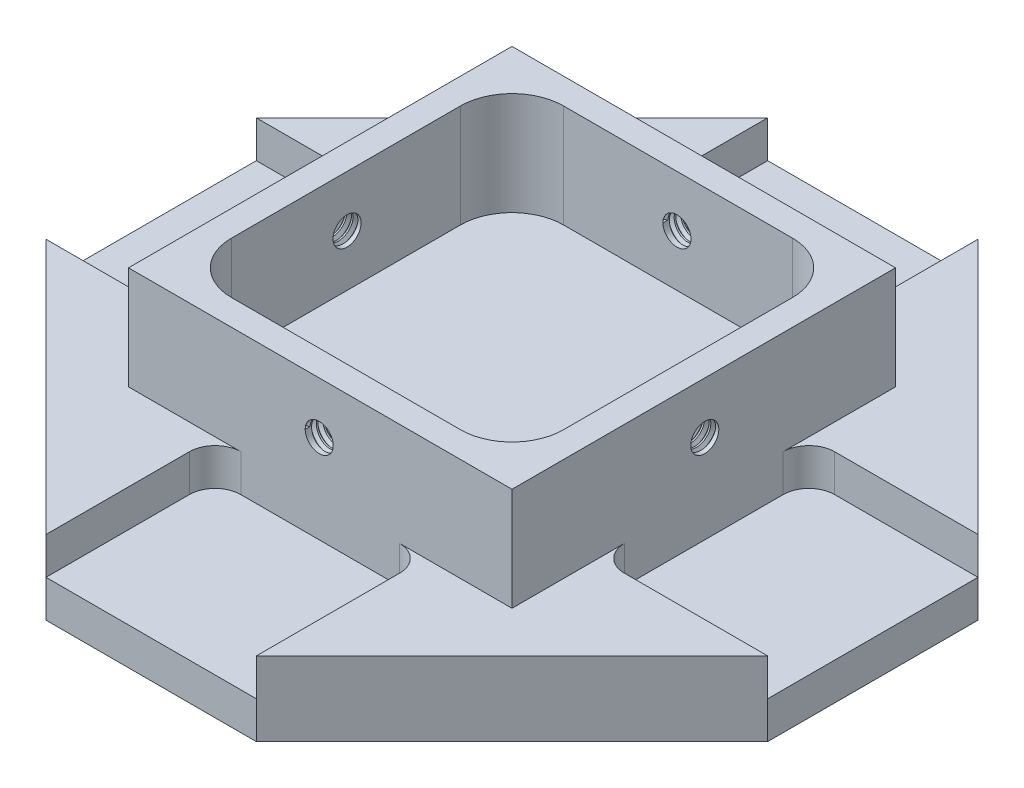
SolidWorks part; units mm, degrees
material "6061 Alloy"
ref_plane "Front Plane" through (0, 0, 0) normal (0, 0, 1) x (1, 0, 0)
ref_plane "Top Plane" through (0, 0, 0) normal (0, 1, 0) x (1, 0, 0)
ref_plane "Right Plane" through (0, 0, 0) normal (1, 0, 0) x (0, 0, -1)
sketch "Sketch1" plane through (0, 0, 0) normal (0, 1, 0) x (1, 0, 0)
  line L1 (0, 0) -> (88.9, 0)
  line L2 (0, 0) -> (0, 88.9)
  line L3 (0, 88.9) -> (88.9, 88.9)
  line L4 (88.9, 0) -> (88.9, 88.9)
  dimension "D1" = 88.9
  dimension "D2" = 88.9
extrude "Boss-Extrude1" add sketch "Sketch1" along normal blind 9.144
sketch "Sketch2" plane through (0, 9.144, 0) normal (0, 1, 0) x (1, 0, 0)
  line L0 (88.9, 88.9) -> (0, 88.9) construction
  line L1 (31.496, 88.9) -> (57.404, 88.9)
  line L2 (31.496, 88.9) -> (31.496, 67.31)
  line L3 (31.496, 67.31) -> (57.404, 67.31)
  line L4 (57.404, 88.9) -> (57.404, 67.31)
  line L5 (0, 88.9) -> (0, 0) construction
  line L6 (0, 57.404) -> (21.59, 57.404)
  line L7 (0, 57.404) -> (0, 31.496)
  line L8 (0, 31.496) -> (21.59, 31.496)
  line L9 (21.59, 57.404) -> (21.59, 31.496)
  line L10 (0, 0) -> (88.9, 0) construction
  line L11 (31.496, 0) -> (57.404, 0)
  line L12 (31.496, 0) -> (31.496, 21.59)
  line L13 (31.496, 21.59) -> (57.404, 21.59)
  line L14 (57.404, 0) -> (57.404, 21.59)
  line L15 (88.9, 0) -> (88.9, 88.9) construction
  line L16 (88.9, 57.404) -> (67.31, 57.404)
  line L17 (88.9, 57.404) -> (88.9, 31.496)
  line L18 (88.9, 31.496) -> (67.31, 31.496)
  line L19 (67.31, 57.404) -> (67.31, 31.496)
  dimension "D1" = 31.496
  dimension "D2" = 25.908
  dimension "D3" = 25.908
  dimension "D4" = 31.496
  dimension "D5" = 25.908
  dimension "D6" = 31.496
  dimension "D7" = 25.908
  dimension "D8" = 31.496
  dimension "D9" = 21.59
  dimension "D10" = 21.59
  dimension "D11" = 21.59
  dimension "D12" = 21.59
extrude "Cut-Extrude1" cut sketch "Sketch2" against normal blind 4.572
sketch "Sketch3" plane through (0, 9.144, 0) normal (0, 1, 0) x (1, 0, 0)
  line L0 (31.496, 88.9) -> (0, 88.9) construction
  line L1 (20.6375, 68.2625) -> (68.2625, 68.2625)
  line L2 (20.6375, 68.2625) -> (20.6375, 20.6375)
  line L3 (20.6375, 20.6375) -> (68.2625, 20.6375)
  line L4 (68.2625, 68.2625) -> (68.2625, 20.6375)
  line L5 (0, 31.496) -> (0, 0) construction
  line L6 (88.9, 31.496) -> (88.9, 57.404) construction
  line L7 (57.404, 88.9) -> (31.496, 88.9) construction
  line L8 (0, 57.404) -> (0, 31.496) construction
  line L9 (31.496, 0) -> (57.404, 0) construction
  circle A0 centre (28.194, 44.45) radius 2.4
  circle A1 centre (44.45, 60.706) radius 2.4
  circle A2 centre (60.706, 44.45) radius 2.4
  circle A3 centre (44.45, 28.194) radius 2.4
  dimension "D5" = 4.8
  dimension "D6" = 4.8
  dimension "D7" = 4.8
  dimension "D8" = 4.8
  dimension "D1" = 47.625
  dimension "D2" = 47.625
  dimension "D3" = 20.6375
  dimension "D4" = 20.6375
  dimension "D9" = 28.194
  dimension "D10" = 28.194
  dimension "D11" = 28.194
  dimension "D12" = 28.194
  dimension "D13" = 23.8125
  dimension "D14" = 23.8125
  dimension "D15" = 23.8125
  dimension "D16" = 23.8125
extrude "Cut-Extrude2" [suppressed] cut sketch "Sketch3" against normal through all contours A2 | A1 | A0 | A3
sketch "Sketch4" plane through (0, 4.572, 0) normal (0, 1, 0) x (1, 0, 0)
  line L0 (0, 57.404) -> (0, 31.496) construction
  line L1 (57.404, 88.9) -> (31.496, 88.9) construction
  line L2 (88.9, 31.496) -> (88.9, 57.404) construction
  line L3 (31.496, 0) -> (57.404, 0) construction
  line L4 (0, 31.496) -> (21.59, 31.496) construction
  line L5 (31.496, 21.59) -> (31.496, 0) construction
  line L6 (67.31, 31.496) -> (88.9, 31.496) construction
  line L7 (57.404, 67.31) -> (57.404, 88.9) construction
  circle A0 centre (79.629, 50.3936) radius 1.8034
  circle A1 centre (79.629, 39.2684) radius 1.8034
  circle A2 centre (49.6316, 79.629) radius 1.8034
  circle A3 centre (38.5064, 79.629) radius 1.8034
  circle A4 centre (9.271, 50.3936) radius 1.8034
  circle A5 centre (9.271, 39.2684) radius 1.8034
  circle A6 centre (39.2684, 9.271) radius 1.8034
  circle A7 centre (50.3936, 9.271) radius 1.8034
  dimension "D1" = 3.6068
  dimension "D2" = 3.6068
  dimension "D3" = 3.6068
  dimension "D4" = 3.6068
  dimension "D5" = 3.6068
  dimension "D6" = 3.6068
  dimension "D7" = 3.6068
  dimension "D8" = 3.6068
  dimension "D9" = 9.271
  dimension "D10" = 9.271
  dimension "D11" = 9.271
  dimension "D12" = 9.271
  dimension "D13" = 9.271
  dimension "D14" = 9.271
  dimension ".313" = 9.271
  dimension "D16" = 9.271
  dimension "D17" = 11.1252
  dimension "D18" = 7.7724
  dimension "D19" = 7.7724
  dimension "D20" = 11.1252
  dimension "D21" = 7.7724
  dimension "D22" = 11.1252
  dimension "D23" = 7.7724
  dimension "D24" = 11.1252
extrude "Cut-Extrude3" [suppressed] cut sketch "Sketch4" against normal through all
sketch "Sketch5" plane through (0, 9.144, 0) normal (0, 1, 0) x (1, 0, 0)
  line L0 (88.9, 88.9) -> (57.404, 88.9) construction
  line L1 (88.9, 31.496) -> (88.9, 57.404) construction
  circle A0 centre (44.45, 44.45) radius 6.35
  dimension "D1" = 12.7
  dimension "D2" = 44.45
  dimension "D3" = 44.45
extrude "Cut-Extrude4" [suppressed] cut sketch "Sketch5" against normal through all
sketch "Sketch6" plane through (0, 9.144, 0) normal (0, 1, 0) x (1, 0, 0)
  line L0 (88.9, 31.496) -> (57.404, 0)
  line L1 (57.404, 0) -> (88.9, 0)
  line L2 (88.9, 0) -> (88.9, 31.496)
extrude "Cut-Extrude5" cut sketch "Sketch6" against normal through all
sketch "Sketch7" plane through (0, 9.144, 0) normal (0, 1, 0) x (1, 0, 0)
  line L0 (0, 88.9) -> (0, 57.404) construction
  line L1 (20.828, 68.072) -> (68.072, 68.072)
  line L2 (20.828, 68.072) -> (20.828, 20.828)
  line L3 (20.828, 20.828) -> (68.072, 20.828)
  line L4 (68.072, 68.072) -> (68.072, 20.828)
  line L5 (0, 0) -> (31.496, 0) construction
  line L7 (24.003, 24.003) -> (64.897, 24.003)
  line L8 (24.003, 24.003) -> (24.003, 64.897)
  line L9 (24.003, 64.897) -> (64.897, 64.897)
  line L10 (64.897, 24.003) -> (64.897, 64.897)
  dimension "D1" = 47.244
  dimension "D2" = 47.244
  dimension "D3" = 20.828
  dimension "D4" = 20.828
  dimension "D5" = 3.175
  dimension "D6" = 3.175
  dimension "D7" = 3.175
  dimension "D8" = 3.175
extrude "Boss-Extrude2" add sketch "Sketch7" along normal blind 12.7 and the other way up to next (4.572 mm away)
fillet "Fillet9" radius 6.35 1 edges at (64.897, 15.494, -24.003)
fillet "Fillet10" radius 6.35 1 edges at (24.003, 15.494, -24.003)
fillet "Fillet11" radius 6.35 1 edges at (64.897, 15.494, -64.897)
fillet "Fillet12" radius 6.35 1 edges at (24.003, 15.494, -64.897)
fillet "Fillet15" radius 3.175 1 edges at (20.828, 6.858, -57.404)
fillet "Fillet16" radius 3.175 1 edges at (31.496, 6.858, -20.828)
fillet "Fillet17" radius 3.175 1 edges at (57.404, 6.858, -20.828)
fillet "Fillet18" radius 3.175 1 edges at (68.072, 6.858, -57.404)
fillet "Fillet19" radius 3.175 1 edges at (68.072, 6.858, -31.496)
fillet "Fillet20" radius 3.175 1 edges at (31.496, 6.858, -68.072)
fillet "Fillet21" radius 3.175 1 edges at (57.404, 6.858, -68.072)
fillet "Fillet22" radius 3.175 1 edges at (20.828, 6.858, -31.496)
sketch "Sketch9" plane through (0, 0, -68.072) normal (0, 0, -1) x (-1, 0, 0)
  line L0 (-68.072, 21.844) -> (-68.072, 9.144) construction
  line L1 (-68.072, 21.844) -> (-20.828, 21.844) construction
  circle A0 centre (-44.323, 15.494) radius 1.7272
  dimension "D1" = 3.4544
  dimension "D2" = 23.749
  dimension "D3" = 6.35
extrude "Cut-Extrude6" cut sketch "Sketch9" against normal through all
sketch "Sketch10" plane through (68.072, 0, 0) normal (1, 0, 0) x (0, 0, -1)
  line L0 (20.828, 21.844) -> (68.072, 21.844) construction
  line L1 (20.828, 21.844) -> (20.828, 9.144) construction
  circle A0 centre (44.577, 15.494) radius 1.7272
  dimension "D1" = 3.4544
  dimension "D2" = 6.35
  dimension "D3" = 23.749
extrude "Cut-Extrude7" cut sketch "Sketch10" against normal through all
sketch "Sketch12" plane through (0, 9.144, 0) normal (0, 1, 0) x (1, 0, 0)
  line L0 (0, 31.496) -> (31.496, 0)
  line L1 (31.496, 0) -> (0, 0)
  line L2 (0, 0) -> (0, 31.496)
  line L3 (57.404, 88.9) -> (88.9, 57.404)
  line L4 (88.9, 57.404) -> (88.9, 88.9)
  line L5 (88.9, 88.9) -> (57.404, 88.9)
  line L6 (0, 57.404) -> (31.496, 88.9)
  line L7 (31.496, 88.9) -> (0, 88.9)
  line L8 (0, 88.9) -> (0, 57.404)
sketch "Sketch14" plane through (0, 0, 0) normal (0, -1, 0) x (1, 0, 0)
  line L0 (60.2924, -60.2924) -> (28.8616, -28.8616) construction
  line L6 (24.003, -58.547) -> (24.003, -30.353) construction
  line L7 (30.353, -24.003) -> (58.547, -24.003) construction
  circle A0 centre (28.8616, -28.8616) radius 2.54
  circle A1 centre (60.2924, -60.2924) radius 2.54
  point P0 (44.577, -44.577)
  dimension "D1" = 44.45
  dimension "D2" = 5.08
  dimension "D3" = 5.08
  dimension "D4" = 20.574
  dimension "D5" = 20.574
extrude "Cut-Extrude9" cut sketch "Sketch14" against normal through all
extrude "Cut-Extrude10" cut sketch "Sketch12" against normal through all
thread "Thread1" pitch 0.7937 method cut profile "Thread Profile1" start angle 0, offset 0, length 0, pitch 0.7937, diameter 3.4544
ref_plane "Plane1" through (42.5958, 15.494, -20.828) normal (0, -1, 0) x (-1, 0, 0)
sketch "Thread Profile1" plane through (42.5958, 15.494, -20.828) normal (0, -1, 0) x (-1, 0, 0)
  line L0 (0, 0) -> (0, 0.7937) construction
  line L1 (0, 0) -> (0.4296, 0.248)
  line L2 (0.4296, 0.248) -> (0.4296, 0.3473)
  line L3 (0.4296, 0.3473) -> (0, 0.5953)
  line L4 (0.4296, 0.2977) -> (0, 0.2977) construction
  line L11 (0, 0) -> (0, 0.5953)
  point P2 (0, 0)
  dimension "Pitch" = 0.7937
  dimension "Profile_Angle" = 60
  dimension "Profile_Land" = 0.0992
  dimension "Profile_Height" = 0.4296
thread "Thread2" pitch 0.7937 method cut profile "Thread Profile2" start angle 0, offset 0, length 0, pitch 0.7937, diameter 3.4544
ref_plane "Plane2" through (68.072, 15.494, -42.8498) normal (0, -1, 0) x (0, 0, 1)
sketch "Thread Profile2" plane through (68.072, 15.494, -42.8498) normal (0, -1, 0) x (0, 0, 1)
  line L0 (0, 0) -> (0, 0.7937) construction
  line L1 (0, 0) -> (0.4296, 0.248)
  line L2 (0.4296, 0.248) -> (0.4296, 0.3473)
  line L3 (0.4296, 0.3473) -> (0, 0.5953)
  line L4 (0.4296, 0.2977) -> (0, 0.2977) construction
  line L11 (0, 0) -> (0, 0.5953)
  point P2 (0, 0)
  dimension "Pitch" = 0.7937
  dimension "Profile_Angle" = 60
  dimension "Profile_Land" = 0.0992
  dimension "Profile_Height" = 0.4296
thread "Thread3" pitch 0.7937 method cut profile "Thread Profile3" start angle 0, offset 0, length 0, pitch 0.7937, diameter 3.4544
ref_plane "Plane3" through (42.5958, 15.494, -64.897) normal (0, -1, 0) x (-1, 0, 0)
sketch "Thread Profile3" plane through (42.5958, 15.494, -64.897) normal (0, -1, 0) x (-1, 0, 0)
  line L0 (0, 0) -> (0, 0.7937) construction
  line L1 (0, 0) -> (0.4296, 0.248)
  line L2 (0.4296, 0.248) -> (0.4296, 0.3473)
  line L3 (0.4296, 0.3473) -> (0, 0.5953)
  line L4 (0.4296, 0.2977) -> (0, 0.2977) construction
  line L11 (0, 0) -> (0, 0.5953)
  point P2 (0, 0)
  dimension "Pitch" = 0.7937
  dimension "Profile_Angle" = 60
  dimension "Profile_Land" = 0.0992
  dimension "Profile_Height" = 0.4296
thread "Thread4" pitch 0.7937 method cut profile "Thread Profile4" start angle 0, offset 0, length 0, pitch 0.7937, diameter 3.4544
ref_plane "Plane4" through (24.003, 15.494, -42.8498) normal (0, -1, 0) x (0, 0, 1)
sketch "Thread Profile4" plane through (24.003, 15.494, -42.8498) normal (0, -1, 0) x (0, 0, 1)
  line L0 (0, 0) -> (0, 0.7937) construction
  line L1 (0, 0) -> (0.4296, 0.248)
  line L2 (0.4296, 0.248) -> (0.4296, 0.3473)
  line L3 (0.4296, 0.3473) -> (0, 0.5953)
  line L4 (0.4296, 0.2977) -> (0, 0.2977) construction
  line L11 (0, 0) -> (0, 0.5953)
  point P2 (0, 0)
  dimension "Pitch" = 0.7937
  dimension "Profile_Angle" = 60
  dimension "Profile_Land" = 0.0992
  dimension "Profile_Height" = 0.4296
equation "\"hinge_hole\"= 0.142in"
equation "\"D1@Sketch4\"=\"hinge_hole\""
equation "\"D2@Sketch4\"=\"hinge_hole\""
equation "\"D3@Sketch4\"=\"hinge_hole\""
equation "\"D4@Sketch4\"=\"hinge_hole\""
equation "\"D5@Sketch4\"=\"hinge_hole\""
equation "\"D6@Sketch4\"=\"hinge_hole\""
equation "\"D7@Sketch4\"=\"hinge_hole\""
equation "\"D8@Sketch4\"=\"hinge_hole\""
equation "\"hinge_hole_dist\"= 0.297 + 0.25"
equation "\"hinge_hole_sep\"=0.438"
equation "\"hinge_hole_from_wall\"= ( 1.05 - .438 ) / 2"
equation "\"D17@Sketch4\"=\"hinge_hole_sep\""
equation "\"D18@Sketch4\"=\"hinge_hole_from_wall\""
equation "\"D19@Sketch4\"=\"hinge_hole_from_wall\""
equation "\"D20@Sketch4\"=\"hinge_hole_sep\""
equation "\"D21@Sketch4\"=\"hinge_hole_from_wall\""
equation "\"D22@Sketch4\"=\"hinge_hole_sep\""
equation "\"D23@Sketch4\"=\"hinge_hole_from_wall\""
equation "\"D24@Sketch4\"=\"hinge_hole_sep\""
equation "\"D9@Sketch2\"=\"hinge_hole_dist\" + (0.6-0.297)"
equation "\"D12@Sketch2\"=\"hinge_hole_dist\" + (0.6-0.297)"
equation "\"D11@Sketch2\"=\"hinge_hole_dist\" + (0.6-0.297)"
equation "\"D10@Sketch2\"=\"hinge_hole_dist\" + (0.6-0.297)"
